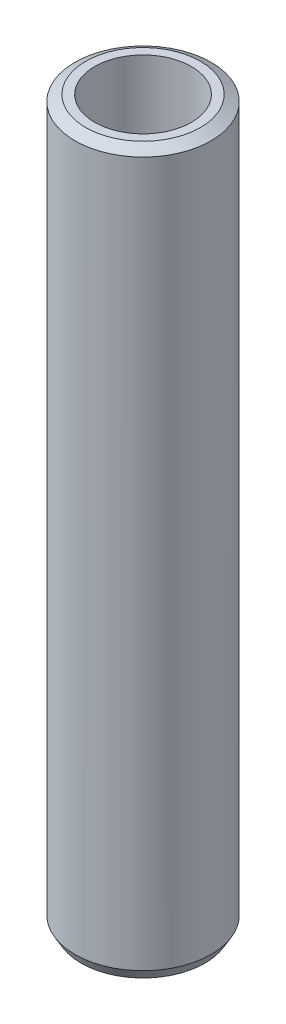
SolidWorks part; units mm, degrees
ref_plane "Front Plane" through (0, 0, 0) normal (0, 0, 1) x (1, 0, 0)
ref_plane "Top Plane" through (0, 0, 0) normal (0, 1, 0) x (1, 0, 0)
ref_plane "Right Plane" through (0, 0, 0) normal (1, 0, 0) x (0, 0, -1)
sketch "Sketch1" plane through (0, 0, 0) normal (0, 1, 0) x (1, 0, 0)
  circle A0 centre (0, 0) radius 22.5
  dimension "SHAFT_OD" = 45
extrude "Boss-Extrude1" add sketch "Sketch1" along normal blind 238.4733
sketch "Sketch2" plane through (0, 0, 0) normal (0, 1, 0) x (1, 0, 0)
  circle A0 centre (0, 0) radius 15.992
  dimension "BORE_D" = 31.984
extrude "Cut-Extrude1" cut sketch "Sketch2" along normal through all
chamfer "Chamfer1" distance 2.0361 angle 60 2 edges at (0, 238.4733, 22.5) (0, 0, 22.5) first distance on face at (0, 238.4733, 22.5) first distance on face at (0, 0, 15.992)
